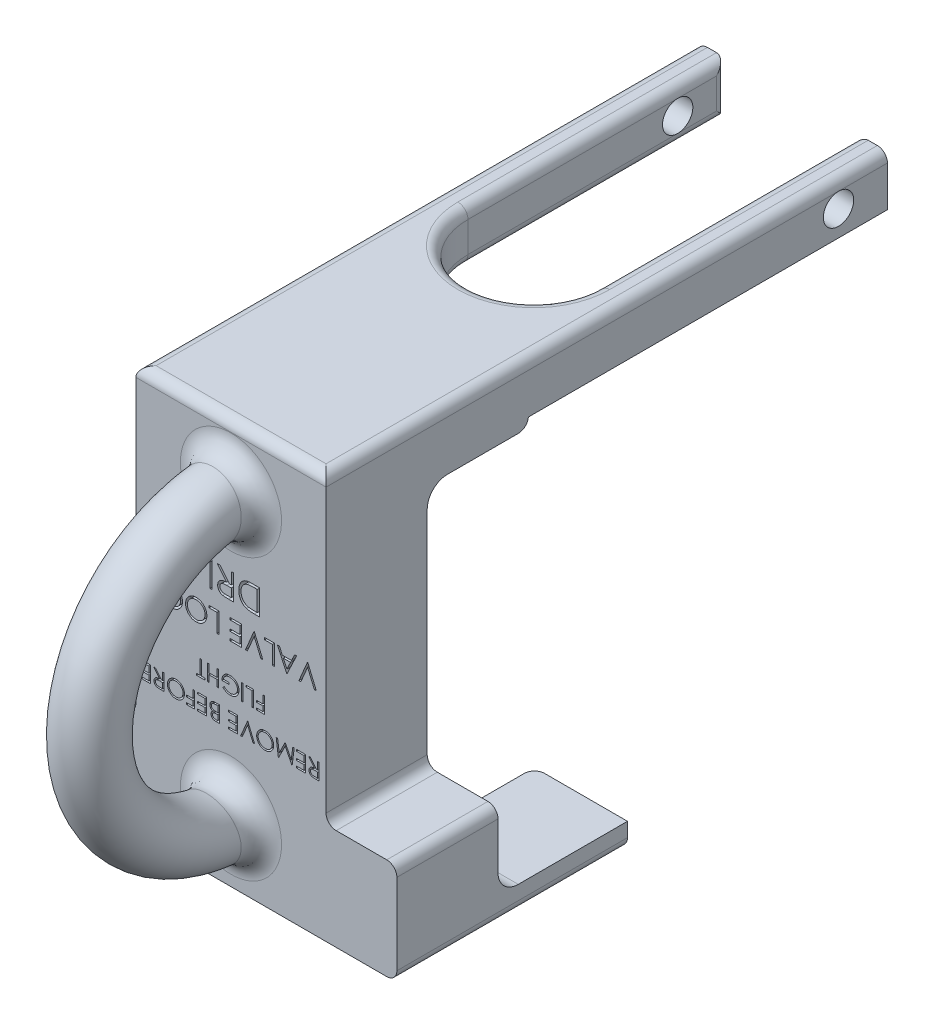
SolidWorks part; units mm, degrees
material "ABS PC"
ref_plane "Front Plane" through (0, 0, 0) normal (0, 0, 1) x (1, 0, 0)
ref_plane "Top Plane" through (0, 0, 0) normal (0, 1, 0) x (1, 0, 0)
ref_plane "Right Plane" through (0, 0, 0) normal (1, 0, 0) x (0, 0, -1)
sketch "Sketch1" plane through (0, 0, 0) normal (0, 0, 1) x (1, 0, 0)
  line L0 (0, 2.5) -> (0, -5) construction
  line L1 (-11.938, -5) -> (11.938, -5)
  line L2 (-11.938, -5) -> (-11.938, 2.5)
  line L3 (-11.938, 2.5) -> (11.938, 2.5)
  line L4 (11.938, -5) -> (11.938, 2.5)
  circle A0 centre (0, 0) radius 1.5
  dimension "D1" = 3
  dimension "D2" = 23.876
  dimension "D3" = 5
  dimension "D4" = 2.5
extrude "Boss-Extrude2" add sketch "Sketch1" along normal blind 25.4 contours L0 L3 L2 L1 A0 | L0 A0 | A0 L0 | L3 L0 A0 L1 L4 region at (6.1881, -1.3014, 0) region at (-6.1881, -1.3014, 0) region at (0.6366, 0, 0) region at (-0.6366, 0, 0)
ref_plane "Plane1" through (0, -1.25, 0) normal (0, 1, 0) x (1, 0, 0)
sketch "Sketch15" plane through (0, 2.5, 0) normal (0, 1, 0) x (1, 0, 0)
  line L0 (-11.938, 0) -> (11.938, 0) construction
  line L1 (-11.938, 0) -> (11.938, 0)
  line L3 (-11.938, 0) -> (11.938, 0)
  line L7 (-8.255, 12.61) -> (8.255, 12.61) construction
  line L10 (-11.938, 0) -> (-11.938, 45.085)
  line L11 (-11.938, 45.085) -> (-8.255, 45.085)
  line L12 (-8.255, 12.61) -> (-8.255, 45.085)
  line L14 (8.255, 12.61) -> (8.255, 45.085)
  line L15 (8.255, 45.085) -> (11.938, 45.085)
  line L16 (11.938, 0) -> (11.938, 45.085)
  arc A0 (-8.255, 12.61) -> (8.255, 12.61) centre (0, 12.61) ccw
  line M5 (11.938, 0) -> (-11.938, 0)
  dimension "D2" = 8.255
  dimension "D1" = 45.085
  dimension "D3" = 12.61
extrude "Boss-Extrude3" add sketch "Sketch15" against normal blind 6.35 contours A0 M5 region at (-11.4278, 2.5, -22.5425)
sketch "Sketch19" plane through (0, -5, 0) normal (0, 1, 0) x (1, 0, 0)
  line L0 (-9.144, -20.32) -> (9.144, -20.32)
  line L1 (-11.938, -25.4) -> (11.938, -25.4) construction
  line L2 (-9.144, -20.32) -> (-9.144, -12.7)
  line L3 (-9.144, -12.7) -> (-11.938, -12.7)
  line L4 (-11.938, -25.4) -> (-11.938, 45.085) construction
  line L5 (-11.938, -12.7) -> (-11.938, -25.4)
  line L6 (-11.938, -25.4) -> (11.938, -25.4)
  line L7 (11.938, -25.4) -> (11.938, -12.7)
  line L8 (11.938, -25.4) -> (11.938, 45.085) construction
  line L9 (11.938, -12.7) -> (9.144, -12.7)
  line L10 (9.144, -12.7) -> (9.144, -20.32)
  point P10 (0, -20.32)
  point P17 (0, -25.4)
  dimension "D1" = 5.08
  dimension "D2" = 18.288
  dimension "D3" = 12.7
extrude "Boss-Extrude4" add sketch "Sketch19" against normal blind 43.18
sketch "Sketch20" plane through (11.938, 0, 0) normal (1, 0, 0) x (0, 0, -1)
  line L0 (45.085, -3.85) -> (45.085, 2.5) construction
  circle A0 centre (38.9382, -0.675) radius 1.905
  point P5 (45.085, -0.675)
  dimension "D2" = 3.81
  dimension "D1" = 6.1468
extrude "Cut-Extrude1" cut sketch "Sketch20" against normal through all
fillet "Fillet1" radius 2.54 2 edges at (9.144, -26.59, 20.32) (-9.144, -26.59, 20.32)
fillet "Fillet2" radius 2.54 2 edges at (-10.541, -5, 12.7) (10.541, -5, 12.7)
fillet "Fillet3" radius 2.54 5 edges at (9.144, -5, 13.97) (8.4001, -5, 19.5761) (0, -5, 20.32) (-8.4001, -5, 19.5761) (-9.144, -5, 13.97)
sketch "Sketch21" plane through (0, 0, 12.7) normal (0, 0, -1) x (-1, 0, 0)
  line L0 (11.938, -48.18) -> (11.938, -7.54) construction
  line L1 (9.144, -48.18) -> (11.938, -48.18)
  line L2 (9.144, -48.18) -> (9.144, -45.132)
  line L3 (9.144, -45.132) -> (11.938, -45.132)
  line L4 (11.938, -48.18) -> (11.938, -45.132)
  line L5 (-11.938, -48.18) -> (-11.938, -7.54) construction
  line L6 (-9.144, -48.18) -> (-11.938, -48.18)
  line L7 (-9.144, -48.18) -> (-9.144, -45.132)
  line L8 (-9.144, -45.132) -> (-11.938, -45.132)
  line L9 (-11.938, -48.18) -> (-11.938, -45.132)
  dimension "D1" = 3.048
extrude "Boss-Extrude5" add sketch "Sketch21" along normal blind 16.256
fillet "Fillet4" radius 2.54 2 edges at (-10.541, -45.132, 12.7) (10.541, -45.132, 12.7)
sketch "Sketch29" plane through (0, 0, 25.4) normal (0, 0, 1) x (1, 0, 0)
  line L0 (11.938, -29.13) -> (-11.938, -29.13) construction
  line L1 (11.938, -48.18) -> (11.938, 2.5) construction
  line L2 (-11.938, -48.18) -> (-11.938, 2.5) construction
  line L3 (11.938, -18.97) -> (-11.938, -18.97) construction
  line L4 (11.938, -25.32) -> (-11.938, -25.32) construction
  line L5 (11.938, -13.89) -> (-11.938, -13.89) construction
  line L6 (-11.938, -48.18) -> (11.938, -48.18) construction
  text T0 "REMOVE BEFORE" font "Century Gothic" height 2.032
  text T1 "FLIGHT" font "Century Gothic" height 2.032
  text T2 "VALVE LOCK" font "Century Gothic" height 2.54
  text T3 "DRL"
  dimension "D1" = 3.81
  dimension "D2" = 19.05
  dimension "D3" = 6.35
  dimension "D4" = 5.08
extrude "Cut-Extrude2" cut sketch "Sketch29" against normal blind 2.54
sketch "Sketch2" plane through (0, -25.38, 0) normal (1, 0, 0) x (0, -1, 0)
  line L1 (22.8, -25.4) -> (-27.88, -25.4) construction
  line L2 (22.8, -25.4) -> (-27.88, -25.4) construction
  arc A0 (-20.32, -25.4) -> (15.24, -25.4) centre (-2.54, -25.4) ccw
  dimension "D1" = 17.78
sweep "Sweep1" add path "Sketch2" circular profile diameter 7.62 parameters "D3"=7.62
fillet "Fillet6" radius 2.54 2 edges at (3.81, -40.62, 25.4) (3.81, -5.06, 25.4)
sketch "Sketch42" plane through (11.938, 0, 0) normal (1, 0, 0) x (0, 0, -1)
  line L0 (-25.4, -35.48) -> (-12.7, -35.48)
  line L10 (0, -5) -> (0, -3.85)
  line L11 (0, -3.85) -> (45.085, -3.85)
  line L12 (45.085, -3.85) -> (45.085, 2.5)
  line L13 (45.085, 2.5) -> (-25.4, 2.5)
  line L14 (-25.4, 2.5) -> (-25.4, -48.18)
  line L15 (-25.4, -48.18) -> (3.556, -48.18)
  line L16 (3.556, -48.18) -> (3.556, -45.132)
  line L17 (3.556, -45.132) -> (-10.16, -45.132)
  line L18 (-12.7, -42.592) -> (-12.7, -7.54)
  line L19 (-10.16, -5) -> (0, -5)
  line L24 (-25.4, -35.48) -> (-25.4, -48.18)
  line L25 (-25.4, -48.18) -> (3.556, -48.18)
  line L26 (3.556, -48.18) -> (3.556, -45.132)
  line L27 (3.556, -45.132) -> (-10.16, -45.132)
  line L28 (-12.7, -42.592) -> (-12.7, -35.48)
  arc A2 (-12.7, -42.592) -> (-10.16, -45.132) centre (-10.16, -42.592) ccw
  arc A3 (-10.16, -5) -> (-12.7, -7.54) centre (-10.16, -7.54) ccw
  arc A4 (-12.7, -42.592) -> (-10.16, -45.132) centre (-10.16, -42.592) ccw
  dimension "D2" = 12.7
  dimension "D1" = 0
extrude "Boss-Extrude6" add sketch "Sketch42" along normal blind 8.89
mirror "Mirror1" about plane through (0, 0, 0) normal (1, 0, 0) of "Boss-Extrude6"
fillet "Fillet7" radius 1.27 13 edges at (11.938, -35.48, 19.05) (-11.938, -35.48, 19.05) (-20.828, -35.48, 19.05) (20.828, -35.48, 19.05) (-20.828, -48.18, 10.922) (20.828, -48.18, 10.922) (9.144, -48.18, 7.112) (8.4001, -48.18, 19.5761) (-9.144, -48.18, 7.112) (-8.4001, -48.18, 19.5761) (9.144, -46.656, -3.556) (-9.144, -46.656, -3.556) (0, -48.18, 20.32)
fillet "Fillet8" radius 1.27 12 edges at (8.255, 2.5, -28.8475) (0, 2.5, -4.355) (8.255, -0.675, -45.085) (-8.255, 2.5, -28.8475) (-8.255, -0.675, -45.085) (11.938, 2.5, -9.8425) (0, 2.5, 25.4) (-11.938, 2.5, -9.8425) (-8.255, -3.85, -28.8475) (8.255, -3.85, -28.8475) (0, -3.85, -4.355) (0, -5, 0)
